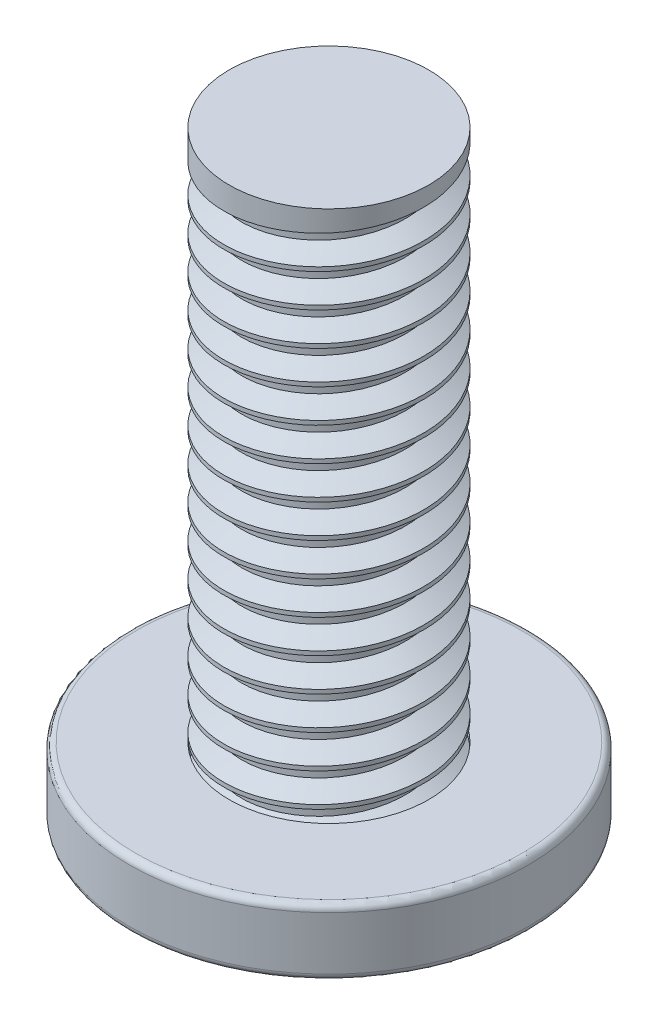
SolidWorks part; units mm, degrees
ref_plane "Front Plane" through (0, 0, 0) normal (0, 0, 1) x (1, 0, 0)
ref_plane "Top Plane" through (0, 0, 0) normal (0, 1, 0) x (1, 0, 0)
ref_plane "Right Plane" through (0, 0, 0) normal (1, 0, 0) x (0, 0, -1)
sketch "Sketch2" plane through (0, 0, 0) normal (0, 1, 0) x (1, 0, 0)
  circle A0 centre (0, 0) radius 3
  dimension "D1" = 6
extrude "Boss-Extrude1" add sketch "Sketch2" along normal blind 1
sketch "Sketch3" plane through (0, 1, 0) normal (0, 1, 0) x (1, 0, 0)
  circle A0 centre (0, 0) radius 1.5
  dimension "D1" = 3
extrude "Boss-Extrude2" add sketch "Sketch3" along normal blind 8
thread "Thread1" pitch 0.5 method cut profile "Thread Profile1" start angle 0, offset 0, length 0, pitch 0.5, diameter 3
ref_plane "Plane1" through (-1.5, 9, 0) normal (0, 0, 1) x (-1, 0, 0)
sketch "Thread Profile1" plane through (-1.5, 9, 0) normal (0, 0, 1) x (-1, 0, 0)
  line L0 (0, 0) -> (0, 0.5) construction
  line L11 (0, 0) -> (0, 0.4375)
  line L12 (0, 0.4375) -> (-0.2706, 0.2812)
  line L13 (-0.2706, 0.2812) -> (-0.2706, 0.1562)
  line L15 (-0.2706, 0.1562) -> (0, 0)
  line L17 (-0.2706, 0.2187) -> (0, 0.2187) construction
  point P2 (0, 0)
  dimension "Pitch" = 0.5
  dimension "Profile_Angle" = 60
  dimension "Profile_Land" = 0.125
  dimension "Profile_Height" = 0.2706
sketch "Sketch13" plane through (0, 0, 0) normal (0, -1, 0) x (1, 0, 0)
  line L1 (1.1547, 0) -> (0.5774, 1)
  line L2 (0.5774, 1) -> (-0.5774, 1)
  line L3 (-0.5774, 1) -> (-1.1547, 0)
  line L4 (-1.1547, 0) -> (-0.5774, -1)
  line L5 (-0.5774, -1) -> (0.5774, -1)
  line L6 (0.5774, -1) -> (1.1547, 0)
  circle A0 centre (0, 0) radius 1 construction
  circle A4 centre (0, 0) radius 3 construction
  dimension "D1" = 2
extrude "Cut-Extrude1" cut sketch "Sketch13" against normal blind 0.5
fillet "Fillet1" radius 0.1 2 edges at (0, 1, 3) (0, 0, 3)
